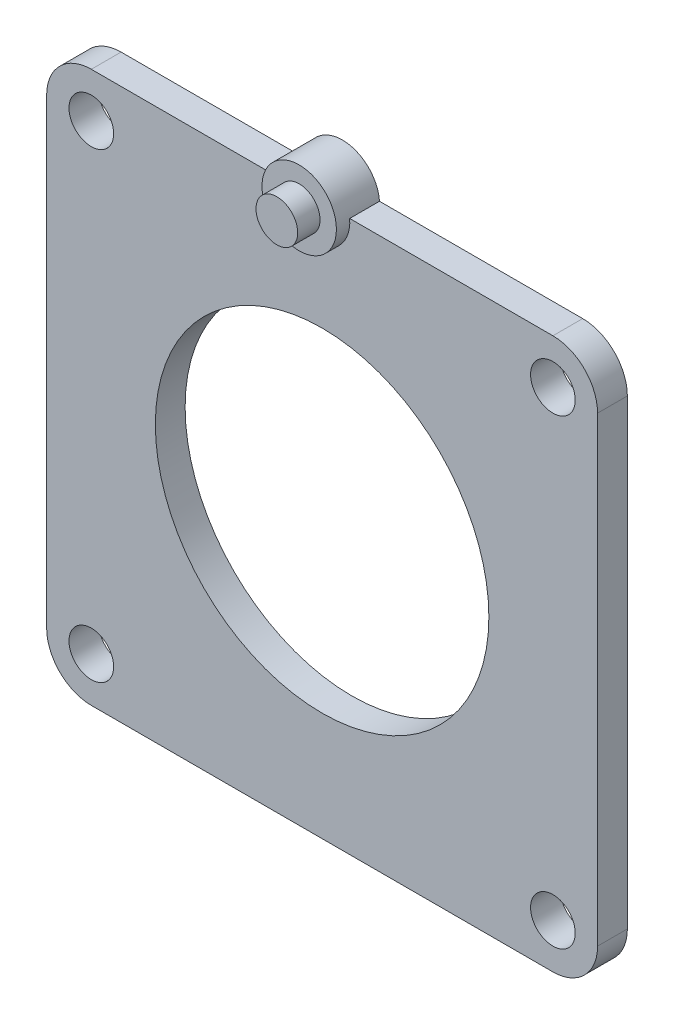
SolidWorks part; units mm, degrees
ref_plane "Front Plane" through (0, 0, 0) normal (0, 0, 1) x (1, 0, 0)
ref_plane "Top Plane" through (0, 0, 0) normal (0, 1, 0) x (1, 0, 0)
ref_plane "Right Plane" through (0, 0, 0) normal (1, 0, 0) x (0, 0, -1)
sketch "Sketch1" plane through (0, 0, 0) normal (0, 0, 1) x (1, 0, 0)
  line L0 (0, 0) -> (17.311, 13.1083) construction
  line L1 (0, 0) -> (-17.311, 13.1083) construction
  line L2 (15.5, 18.5) -> (-15.5, 18.5) construction
  line L3 (-18.5, 15.5) -> (-18.5, -15.5)
  line L4 (18.5, 15.5) -> (18.5, -15.5)
  line L5 (0, 0) -> (-0.6397, 18.32) construction
  line L6 (0, 0) -> (99.0761, 0) construction
  line L7 (15.5, -18.5) -> (-15.5, -18.5)
  line L8 (15.5, 18.5) -> (1.8538, 18.5)
  line L9 (-3.1333, 18.5) -> (-15.5, 18.5)
  circle A0 centre (0, 0) radius 11.2 construction
  circle A1 centre (15.5, 15.5) radius 1.5
  circle A2 centre (-15.5, 15.5) radius 1.5
  circle A3 centre (15.5, 15.5) radius 3 construction
  circle A4 centre (-15.5, 15.5) radius 3 construction
  circle A5 centre (0, 0) radius 11.2
  arc A6 (15.5, 18.5) -> (18.5, 15.5) centre (15.5, 15.5) cw
  arc A7 (18.5, -15.5) -> (15.5, -18.5) centre (15.5, -15.5) cw
  circle A8 centre (-0.6397, 18.32) radius 2.5 construction
  arc A9 (-3.1333, 18.5) -> (1.8538, 18.5) centre (-0.6397, 18.32) cw
  circle A10 centre (15.5, -15.5) radius 1.5
  circle A11 centre (-15.5, -15.5) radius 1.5
  circle A12 centre (15.5, -15.5) radius 3 construction
  circle A13 centre (-15.5, -15.5) radius 3 construction
  arc A14 (-15.5, -18.5) -> (-18.5, -15.5) centre (-15.5, -15.5) cw
  arc A15 (-18.5, 15.5) -> (-15.5, 18.5) centre (-15.5, 15.5) cw
  point P0 (0, 0)
  point P1 (15.5, 15.5)
  point P3 (-15.5, 15.5)
  point P20 (-0.6397, 18.32)
  point P25 (-15.5, -15.5)
  point P26 (15.5, -15.5)
  dimension "D1" = 15.5
  dimension "D5" = 18.3312
  dimension "D6" = 15.5
  dimension "D10" = 92
  dimension "D2" = 15.5
  dimension "D3" = 15.5
  dimension "D4" = 15.5
  dimension "D7" = 15.5
  dimension "D8" = 15.5
  dimension "D9" = 15.5
extrude "Extrude1" add sketch "Sketch1" along normal blind 2
sketch "Sketch2" plane through (0, 0, 2) normal (0, 0, 1) x (1, 0, 0)
  circle A0 centre (-0.6397, 18.32) radius 2.5
extrude "Extrude2" add sketch "Sketch2" along normal blind 0.9
sketch "Sketch3" plane through (0, 0, 2.9) normal (0, 0, 1) x (1, 0, 0)
  circle A0 centre (-0.6397, 18.32) radius 1.4
extrude "Extrude3" add sketch "Sketch3" along normal blind 1.5
